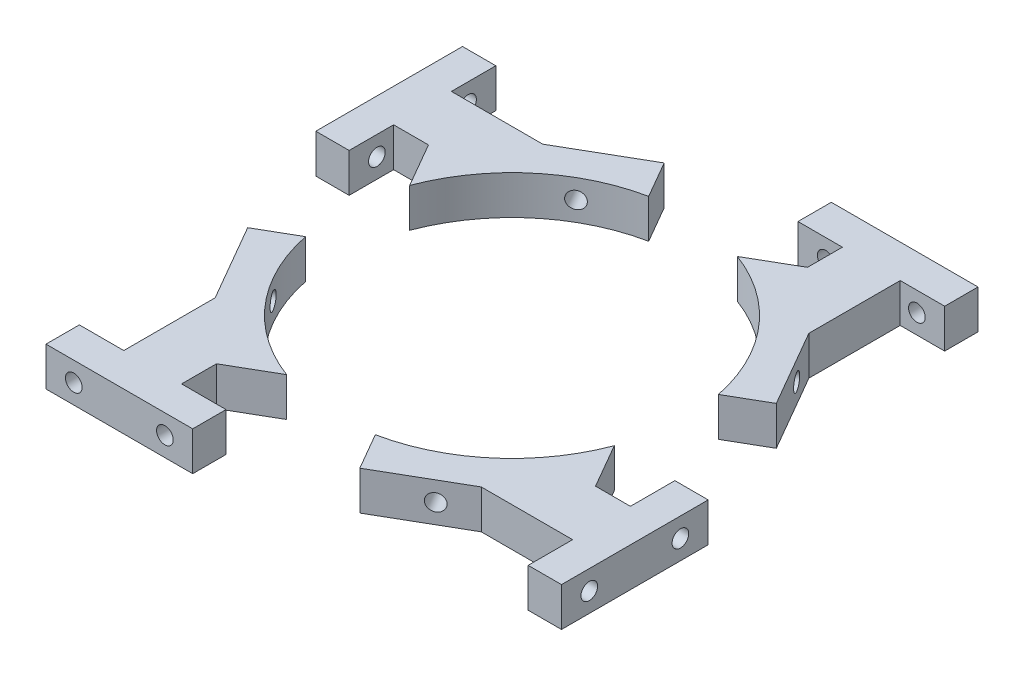
SolidWorks part; units mm, degrees
ref_plane "Front Plane" through (0, 0, 0) normal (0, 0, 1) x (1, 0, 0)
ref_plane "Top Plane" through (0, 0, 0) normal (0, 1, 0) x (1, 0, 0)
ref_plane "Right Plane" through (0, 0, 0) normal (1, 0, 0) x (0, 0, -1)
sketch "Sketch1" plane through (0, 0, 0) normal (0, 1, 0) x (1, 0, 0)
  line L0 (0, -46.3839) -> (25.6451, -46.3839) construction
  line L1 (0, 46.3839) -> (25.6458, 46.3839) construction
  line L2 (0, 0) -> (0, 46.3839) construction
  line L3 (0, 0) -> (0, -46.3839) construction
  line L4 (0, 0) -> (27.2798, 15.75) construction
  line L5 (27.2798, 15.75) -> (-27.2798, 15.75) construction
  line L6 (-27.2798, 15.75) -> (0, 0) construction
  circle A0 centre (0, 0) radius 31.5
  dimension "D1" = 63
  dimension "D2" = 46.3839
  dimension "D3" = 25.6458
  dimension "D4" = 60
extrude "Boss-Extrude1" add sketch "Sketch1" against normal mid plane 7
ref_plane "Plane1" through (27.2798, 0, -15.75) normal (0.866, 0, -0.5) x (-0.5, 0, -0.866)
sketch "Sketch2" plane through (27.2798, 0, -15.75) normal (0.866, 0, -0.5) x (-0.5, 0, -0.866)
  circle A0 centre (0, 0) radius 1.5
  dimension "D1" = 3
extrude "Cut-Extrude1" cut sketch "Sketch2" against normal blind 4
ref_axis "Axis1" through (0, -3.5, 0) along (0, 1, 0)
pattern_circular "CirPattern1" count 6 over 360 about axis through (0, -3.5, 0) along (0, 1, 0) of "Cut-Extrude1"
sketch "Sketch3" plane through (27.2798, 0, -15.75) normal (0.866, 0, -0.5) x (-0.5, 0, -0.866)
  line L0 (-31.5, -3.5) -> (31.5, -3.5) construction
  line L1 (20, -3.5) -> (-10, -3.5)
  line L2 (20, -3.5) -> (20, 3.5)
  line L3 (20, 3.5) -> (-10, 3.5)
  line L4 (-10, -3.5) -> (-10, 3.5)
  line L5 (31.5, 3.5) -> (-31.5, 3.5) construction
  circle A0 centre (0, 0) radius 1.5
  dimension "D3" = 3
  dimension "D1" = 10
  dimension "D2" = 20
extrude "Boss-Extrude2" add sketch "Sketch3" along normal blind 6 and the other way up to surface separate body other way up to face at (26.5204, -0.3431, 16.9977)
ref_plane "Plane2" through (0, 0, -46.3839) normal (0, 0, 1) x (1, 0, 0)
sketch "Sketch5" plane through (32.476, 0, -18.75) normal (0.866, 0, -0.5) x (-0.5, 0, -0.866)
  line L0 (6, -3.5) -> (6, 3.5) construction
  line L1 (-10, -3.5) -> (20, -3.5) construction
  line L2 (20, 3.5) -> (-10, 3.5) construction
  dimension "D1" = 6
sketch "Sketch6" plane through (0, 0, -46.3839) normal (0, 0, 1) x (1, 0, 0)
  line L0 (37.476, 0) -> (11.0758, 0) construction
  line L1 (11.0758, -3.5) -> (37.476, -3.5)
  line L2 (11.0758, -3.5) -> (11.0758, 3.5)
  line L3 (11.0758, 3.5) -> (37.476, 3.5)
  line L4 (37.476, -3.5) -> (37.476, 3.5)
  circle A0 centre (32.476, 0) radius 1.5
  circle A1 centre (16.0758, 0) radius 1.5
  dimension "D1" = 3
  dimension "D2" = 5
  dimension "D3" = 5
extrude "Boss-Extrude3" add sketch "Sketch6" along normal blind 6 separate body
sketch "Sketch7" plane through (0, 0, -40.3839) normal (0, 0, 1) x (1, 0, 0)
  line L0 (11.0758, -3.5) -> (37.476, -3.5) construction
  line L1 (29.476, 3.5) -> (19.0758, 3.5)
  line L2 (29.476, 3.5) -> (29.476, -3.5)
  line L3 (29.476, -3.5) -> (19.0758, -3.5)
  line L4 (19.0758, 3.5) -> (19.0758, -3.5)
  circle A0 centre (32.476, 0) radius 1.5 construction
  circle A1 centre (16.0758, 0) radius 1.5 construction
  dimension "D1" = 3
  dimension "D2" = 3
extrude "Boss-Extrude4" add sketch "Sketch7" along normal up to next
delete or keep bodies "Body-Delete/Keep 2" type delete bodies bodies 103
pattern_circular "CirPattern2" count 4 over 360 about axis through (0, -3.5, 0) along (0, 1, 0) of bodies 106
